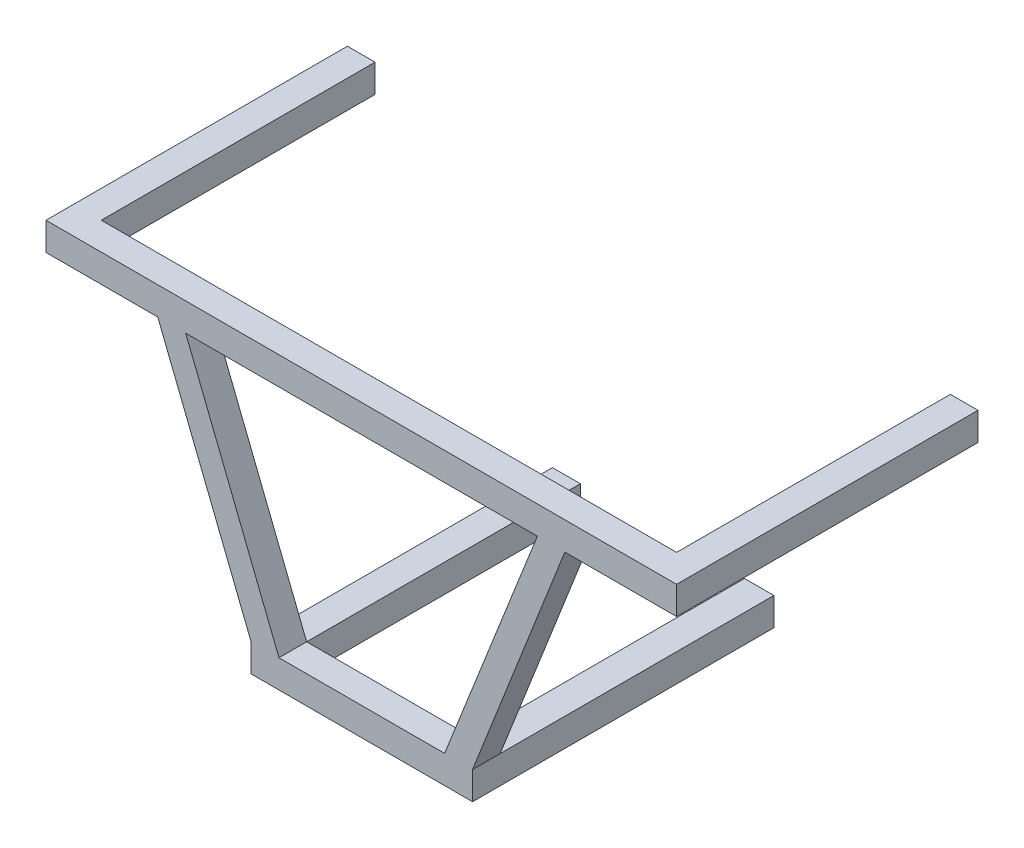
SolidWorks part; units mm, degrees
note: The reader was unsure of these and kept them because the rebuilt part matched: shared geometry of "Sketch1<3>", "Sketch1<4>".
ref_plane "Front Plane" through (0, 0, 0) normal (0, 0, 1) x (1, 0, 0)
ref_plane "Top Plane" through (0, 0, 0) normal (0, 1, 0) x (1, 0, 0)
ref_plane "Right Plane" through (0, 0, 0) normal (1, 0, 0) x (0, 0, -1)
sketch "Sketch1" plane through (0, 0, 0) normal (0, 0, 1) x (1, 0, 0)
  line L0 (0, 53.1321) -> (-114.022, 53.1321) construction
  line L1 (-114.022, 53.1321) -> (114.022, 53.1321) construction
  line L2 (114.022, 53.1321) -> (114.022, 43.0289) construction
  line L3 (114.022, 43.0289) -> (-114.022, 43.0289) construction
  line L4 (0, 53.1321) -> (0, -51.8692) construction
  line L5 (0, -51.8692) -> (40.2324, -51.8692) construction
  line L6 (40.2324, -51.8692) -> (40.2324, -41.766) construction
  line L7 (40.2324, -41.766) -> (-39.8716, -41.766) construction
  line L8 (-39.8716, -41.766) -> (-39.8716, -51.8692) construction
  line L9 (0, 43.0289) -> (-73.6091, 43.0289) construction
  line L10 (-73.6091, 43.0289) -> (73.6091, 43.0289) construction
  line L11 (73.6091, 43.0289) -> (40.2324, -41.766) construction
  line L12 (73.6091, 43.0289) -> (40.2324, -41.766)
  line L13 (-114.022, 53.1321) -> (114.022, 53.1321)
  line L14 (-114.022, 53.1321) -> (-114.022, 43.0289)
  line L15 (-114.022, 43.0289) -> (114.022, 43.0289)
  line L16 (114.022, 53.1321) -> (114.022, 43.0289)
  line L17 (-39.8716, -41.766) -> (40.2324, -41.766)
  line L18 (-39.8716, -41.766) -> (-39.8716, -51.8692)
  line L19 (-39.8716, -51.8692) -> (40.2324, -51.8692)
  line L20 (40.2324, -41.766) -> (40.2324, -51.8692)
  line L21 (-39.8716, -41.766) -> (-73.6091, 43.0289)
  line L22 (-73.6091, 43.0289) -> (-63.5059, 43.0289)
  line L23 (-63.5059, 43.0289) -> (-29.7684, -41.766)
  line L24 (-29.7684, -41.766) -> (-39.8716, -41.766)
  line L25 (40.2324, -41.766) -> (30.1292, -41.766)
  line L26 (30.1292, -41.766) -> (63.6863, 43.0289)
extrude "Extrude1" add sketch "Sketch1" along normal blind 10
extrude "Extrude2" add sketch "Sketch1<3>" along normal blind 10
sketch "Sketch1<3>" plane through (0, 0, 0) normal (0, 0, 1) x (1, 0, 0) same geometry as "Sketch1"
extrude "Extrude3" add sketch "Sketch1<4>" along normal blind 10
sketch "Sketch1<4>" plane through (0, 0, 0) normal (0, 0, 1) x (1, 0, 0) same geometry as "Sketch1"
sketch "Sketch2" plane through (0, 0, 0) normal (0, 0, 1) x (1, 0, 0)
  line L0 (-114.022, 43.0289) -> (114.022, 43.0289) construction
  line L1 (-114.022, 53.1321) -> (-104.0235, 53.1321)
  line L2 (-114.022, 53.1321) -> (-114.022, 43.0289)
  line L3 (-114.022, 43.0289) -> (-104.0235, 43.0289)
  line L4 (-104.0235, 53.1321) -> (-104.0235, 43.0289)
  line L5 (-39.8716, -51.8692) -> (40.2324, -51.8692) construction
  line L6 (-39.8716, -41.766) -> (-29.7684, -41.766)
  line L7 (-39.8716, -41.766) -> (-39.8716, -51.8692)
  line L8 (-39.8716, -51.8692) -> (-29.7684, -51.8692)
  line L9 (-29.7684, -41.766) -> (-29.7684, -51.8692)
  line L11 (40.2324, -41.766) -> (29.5889, -41.766)
  line L12 (40.2324, -41.766) -> (40.2324, -51.8692)
  line L13 (40.2324, -51.8692) -> (29.5889, -51.8692)
  line L14 (29.5889, -41.766) -> (29.5889, -51.8692)
  line L15 (114.022, 53.1321) -> (104.0235, 53.1321)
  line L16 (114.022, 53.1321) -> (114.022, 43.0289)
  line L17 (114.022, 43.0289) -> (104.0235, 43.0289)
  line L18 (104.0235, 53.1321) -> (104.0235, 43.0289)
extrude "Extrude4" add sketch "Sketch2" along normal blind 10 and the other way blind 99
